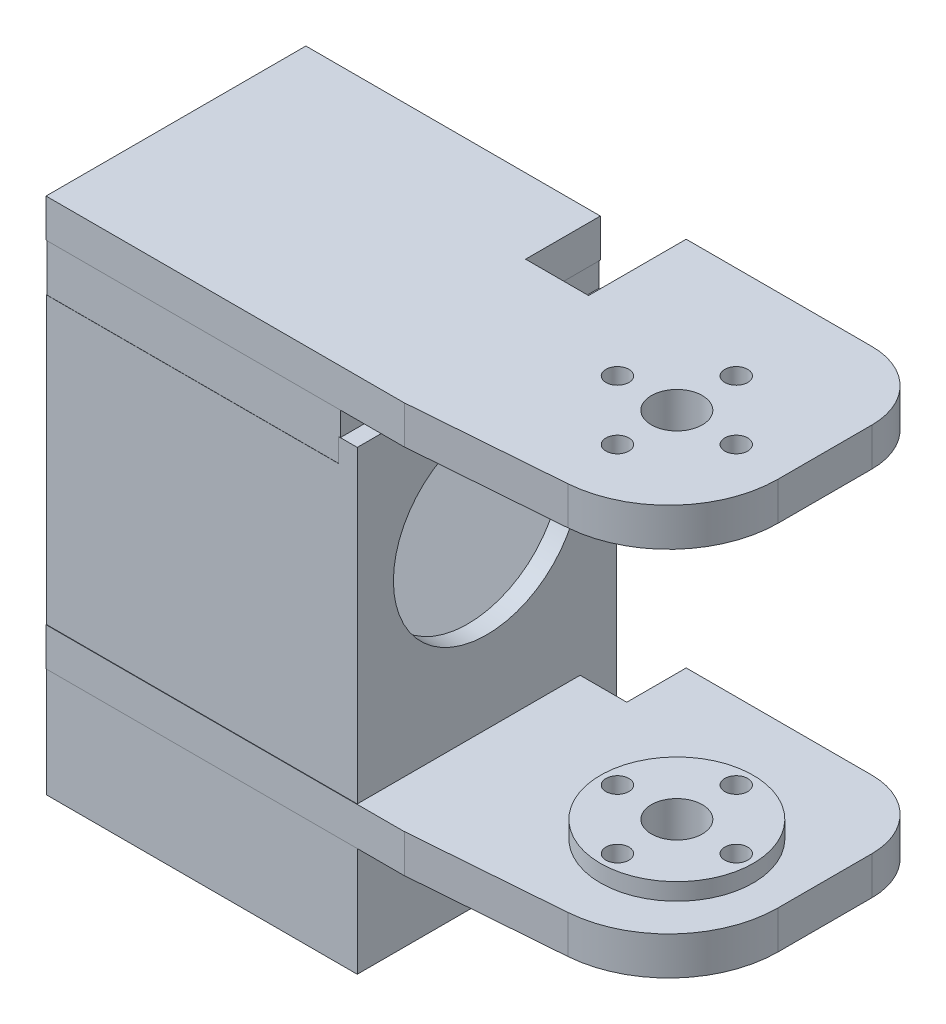
SolidWorks part; units mm, degrees
ref_plane "Front Plane" through (0, 0, 0) normal (0, 0, 1) x (1, 0, 0)
ref_plane "Top Plane" through (0, 0, 0) normal (0, 1, 0) x (1, 0, 0)
ref_plane "Right Plane" through (0, 0, 0) normal (1, 0, 0) x (0, 0, -1)
ref_plane "PY_p18_625" through (0, 18.625, 0) normal (0, 1, 0) x (1, 0, 0)
sketch "S_prism1" plane through (0, 18.625, 0) normal (0, 1, 0) x (1, 0, 0)
  line L0 (13, 10) -> (13, -1.0582)
  line L1 (1.0937, -13.9199) -> (-16.9, -15.31)
  line L2 (-16.9, -15.31) -> (-16.9, 18)
  line L3 (-16.9, 18) -> (5, 18)
  arc A0 (5, 18) -> (13, 10) centre (5.0002, 10.0002) cw
  arc A1 (13, -1.0582) -> (1.0937, -13.9199) centre (0.0999, -1.0582) cw
extrude "Boss_1" add sketch "S_prism1" along normal blind 4.5
ref_plane "PY_m20_625" through (0, -20.625, 0) normal (0, 1, 0) x (1, 0, 0)
sketch "S_cyl2" plane through (0, -20.625, 0) normal (0, 1, 0) x (1, 0, 0)
  circle A0 centre (0, 0) radius 9
  dimension "D1_S_cyl2" = 18
extrude "Boss_2" add sketch "S_cyl2" along normal blind 2
ref_plane "PY_m25_125" through (0, -25.125, 0) normal (0, 1, 0) x (1, 0, 0)
sketch "S_prism3" plane through (0, -25.125, 0) normal (0, 1, 0) x (1, 0, 0)
  line L0 (13, 10) -> (13, -1.0582)
  line L1 (1.0937, -13.9199) -> (-16.9, -15.31)
  line L2 (-16.9, -15.31) -> (-16.9, 18)
  line L3 (-16.9, 18) -> (5, 18)
  arc A0 (5, 18) -> (13, 10) centre (5.0002, 10.0002) cw
  arc A1 (13, -1.0582) -> (1.0937, -13.9199) centre (0.0999, -1.0582) cw
extrude "Boss_3" add sketch "S_prism3" along normal blind 4.5
sketch "S_prism4" plane through (0, 18.625, 0) normal (0, 1, 0) x (1, 0, 0)
  line L0 (-24.575, 6.5) -> (-16.8, 6.5)
  line L1 (-16.8, 6.5) -> (-16.8, -15.31)
  line L2 (-16.8, -15.31) -> (-24.575, -15.31)
  line L3 (-24.575, -15.31) -> (-24.575, 6.5)
extrude "Boss_4" add sketch "S_prism4" along normal blind 4.5
sketch "S_prism5" plane through (0, 18.625, 0) normal (0, 1, 0) x (1, 0, 0)
  line L0 (-59.025, -12.71) -> (-16.8, -12.71)
  line L1 (-16.8, -12.71) -> (-16.8, -15.31)
  line L2 (-16.8, -15.31) -> (-59.025, -15.31)
  line L3 (-59.025, -15.31) -> (-59.025, -12.71)
extrude "Boss_5" add sketch "S_prism5" along normal blind 4.5
sketch "S_prism6" plane through (0, 18.625, 0) normal (0, 1, 0) x (1, 0, 0)
  line L0 (-59.025, 15.31) -> (-24.325, 15.31)
  line L1 (-24.325, 15.31) -> (-24.325, -15.31)
  line L2 (-24.325, -15.31) -> (-59.025, -15.31)
  line L3 (-59.025, -15.31) -> (-59.025, 15.31)
extrude "Boss_6" add sketch "S_prism6" along normal blind 4.5
sketch "S_prism7" plane through (0, -25.125, 0) normal (0, 1, 0) x (1, 0, 0)
  line L0 (-24.575, 11) -> (-16.8, 11)
  line L1 (-16.8, 11) -> (-16.8, -15.31)
  line L2 (-16.8, -15.31) -> (-24.575, -15.31)
  line L3 (-24.575, -15.31) -> (-24.575, 11)
extrude "Boss_7" add sketch "S_prism7" along normal blind 4.5
sketch "S_prism8" plane through (0, -25.125, 0) normal (0, 1, 0) x (1, 0, 0)
  line L0 (-59.025, -12.71) -> (-16.8, -12.71)
  line L1 (-16.8, -12.71) -> (-16.8, -15.31)
  line L2 (-16.8, -15.31) -> (-59.025, -15.31)
  line L3 (-59.025, -15.31) -> (-59.025, -12.71)
extrude "Boss_8" add sketch "S_prism8" along normal blind 4.5
ref_plane "PZ_m15_260" through (0, 0, -15.26) normal (0, 0, 1) x (1, 0, 0)
sketch "S_box9" plane through (0, 0, -15.26) normal (0, 0, 1) x (1, 0, 0)
  line L0 (-59.025, 10.51) -> (-24.625, 10.51)
  line L1 (-24.625, 10.51) -> (-24.625, 13.01)
  line L2 (-24.625, 13.01) -> (-59.025, 13.01)
  line L3 (-59.025, 13.01) -> (-59.025, 10.51)
  dimension "P1" = 59.025
  dimension "P2" = 10.51
  dimension "P3" = 24.625
  dimension "P4" = 10.51
  dimension "P5" = 24.625
  dimension "P6" = 13.01
  dimension "P7" = 59.025
  dimension "P8" = 13.01
extrude "Boss_9" add sketch "S_box9" along normal blind 30.52
sketch "S_box10" plane through (0, 0, -15.26) normal (0, 0, 1) x (1, 0, 0)
  line L0 (-59.025, -38.01) -> (-24.625, -38.01)
  line L1 (-24.625, -38.01) -> (-24.625, 13.01)
  line L2 (-24.625, 13.01) -> (-59.025, 13.01)
  line L3 (-59.025, 13.01) -> (-59.025, -38.01)
  dimension "P1" = 59.025
  dimension "P2" = 38.01
  dimension "P3" = 24.625
  dimension "P4" = 38.01
  dimension "P5" = 24.625
  dimension "P6" = 13.01
  dimension "P7" = 59.025
  dimension "P8" = 13.01
extrude "Boss_10" add sketch "S_box10" along normal blind 2.5
ref_plane "PZ_p12_760" through (0, 0, 12.76) normal (0, 0, 1) x (1, 0, 0)
sketch "S_box11" plane through (0, 0, 12.76) normal (0, 0, 1) x (1, 0, 0)
  line L0 (-59.025, -38.01) -> (-24.625, -38.01)
  line L1 (-24.625, -38.01) -> (-24.625, 13.01)
  line L2 (-24.625, 13.01) -> (-59.025, 13.01)
  line L3 (-59.025, 13.01) -> (-59.025, -38.01)
  dimension "P1" = 59.025
  dimension "P2" = 38.01
  dimension "P3" = 24.625
  dimension "P4" = 38.01
  dimension "P5" = 24.625
  dimension "P6" = 13.01
  dimension "P7" = 59.025
  dimension "P8" = 13.01
extrude "Boss_11" add sketch "S_box11" along normal blind 2.5
sketch "S_box12" plane through (0, 0, -15.26) normal (0, 0, 1) x (1, 0, 0)
  line L0 (-59.025, -38.01) -> (-56.625, -38.01)
  line L1 (-56.625, -38.01) -> (-56.625, 13.01)
  line L2 (-56.625, 13.01) -> (-59.025, 13.01)
  line L3 (-59.025, 13.01) -> (-59.025, -38.01)
  dimension "P1" = 59.025
  dimension "P2" = 38.01
  dimension "P3" = 56.625
  dimension "P4" = 38.01
  dimension "P5" = 56.625
  dimension "P6" = 13.01
  dimension "P7" = 59.025
  dimension "P8" = 13.01
extrude "Boss_12" add sketch "S_box12" along normal blind 30.52
sketch "S_box13" plane through (0, 0, -15.26) normal (0, 0, 1) x (1, 0, 0)
  line L0 (-24.625, -38.01) -> (-22.4, -38.01)
  line L1 (-22.4, -38.01) -> (-22.4, 15.76)
  line L2 (-22.4, 15.76) -> (-24.625, 15.76)
  line L3 (-24.625, 15.76) -> (-24.625, -38.01)
  dimension "P1" = 24.625
  dimension "P2" = 38.01
  dimension "P3" = 22.4
  dimension "P4" = 38.01
  dimension "P5" = 22.4
  dimension "P6" = 15.76
  dimension "P7" = 24.625
  dimension "P8" = 15.76
extrude "Boss_13" add sketch "S_box13" along normal blind 30.52
ref_plane "PZ_m15_240" through (0, 0, -15.24) normal (0, 0, 1) x (1, 0, 0)
sketch "S_box14" plane through (0, 0, -15.24) normal (0, 0, 1) x (1, 0, 0)
  line L0 (-58.955, 12.9) -> (-24.395, 12.9)
  line L1 (-24.395, 12.9) -> (-24.395, 18.725)
  line L2 (-24.395, 18.725) -> (-58.955, 18.725)
  line L3 (-58.955, 18.725) -> (-58.955, 12.9)
  dimension "P1" = 58.955
  dimension "P2" = 12.9
  dimension "P3" = 24.395
  dimension "P4" = 12.9
  dimension "P5" = 24.395
  dimension "P6" = 18.725
  dimension "P7" = 58.955
  dimension "P8" = 18.725
extrude "Boss_14" add sketch "S_box14" along normal blind 30.48
ref_plane "PY_p18_525" through (0, 18.525, 0) normal (0, 1, 0) x (1, 0, 0)
sketch "S_hole15" plane through (0, 18.525, 0) normal (0, 1, 0) x (1, 0, 0)
  circle A0 centre (0, 0) radius 3
  dimension "D1_S_hole15" = 6
extrude "Hole_15" cut sketch "S_hole15" along normal blind 4.7
sketch "S_hole16" plane through (0, 18.525, 0) normal (0, 1, 0) x (1, 0, 0)
  circle A0 centre (7, 0) radius 1.35
  dimension "D1_S_hole16" = 2.7
  dimension "P2" = 7
extrude "Hole_16" cut sketch "S_hole16" along normal blind 4.7
sketch "S_hole17" plane through (0, 18.525, 0) normal (0, 1, 0) x (1, 0, 0)
  circle A0 centre (0, -7) radius 1.35
  dimension "D1_S_hole17" = 2.7
  dimension "P2" = 7
extrude "Hole_17" cut sketch "S_hole17" along normal blind 4.7
sketch "S_hole18" plane through (0, 18.525, 0) normal (0, 1, 0) x (1, 0, 0)
  circle A0 centre (-7, 0) radius 1.35
  dimension "D1_S_hole18" = 2.7
  dimension "P2" = 7
extrude "Hole_18" cut sketch "S_hole18" along normal blind 4.7
sketch "S_hole19" plane through (0, 18.525, 0) normal (0, 1, 0) x (1, 0, 0)
  circle A0 centre (0, 7) radius 1.35
  dimension "D1_S_hole19" = 2.7
  dimension "P2" = 7
extrude "Hole_19" cut sketch "S_hole19" along normal blind 4.7
ref_plane "PY_m25_225" through (0, -25.225, 0) normal (0, 1, 0) x (1, 0, 0)
sketch "S_hole20" plane through (0, -25.225, 0) normal (0, 1, 0) x (1, 0, 0)
  circle A0 centre (0, 0) radius 3
  dimension "D1_S_hole20" = 6
extrude "Hole_20" cut sketch "S_hole20" along normal blind 6.7
sketch "S_hole21" plane through (0, -25.225, 0) normal (0, 1, 0) x (1, 0, 0)
  circle A0 centre (7, 0) radius 1.35
  dimension "D1_S_hole21" = 2.7
  dimension "P2" = 7
extrude "Hole_21" cut sketch "S_hole21" along normal blind 6.7
sketch "S_hole22" plane through (0, -25.225, 0) normal (0, 1, 0) x (1, 0, 0)
  circle A0 centre (0, -7) radius 1.35
  dimension "D1_S_hole22" = 2.7
  dimension "P2" = 7
extrude "Hole_22" cut sketch "S_hole22" along normal blind 6.7
sketch "S_hole23" plane through (0, -25.225, 0) normal (0, 1, 0) x (1, 0, 0)
  circle A0 centre (-7, 0) radius 1.35
  dimension "D1_S_hole23" = 2.7
  dimension "P2" = 7
extrude "Hole_23" cut sketch "S_hole23" along normal blind 6.7
sketch "S_hole24" plane through (0, -25.225, 0) normal (0, 1, 0) x (1, 0, 0)
  circle A0 centre (0, 7) radius 1.35
  dimension "D1_S_hole24" = 2.7
  dimension "P2" = 7
extrude "Hole_24" cut sketch "S_hole24" along normal blind 6.7
ref_plane "PX_m59_125" through (-59.125, 0, 0) normal (1, 0, 0) x (0, 0, -1)
sketch "S_hole25" plane through (-59.125, 0, 0) normal (1, 0, 0) x (0, 0, -1)
  circle A0 centre (0, 0) radius 11
  dimension "D1_S_hole25" = 22
extrude "Hole_25" cut sketch "S_hole25" along normal blind 2.6
sketch "S_hole26" plane through (-59.125, 0, 0) normal (1, 0, 0) x (0, 0, -1)
  circle A0 centre (-10.25, -8.3) radius 1.1
  dimension "D1_S_hole26" = 2.2
  dimension "P2" = 10.25
  dimension "P3" = 8.3
extrude "Hole_26" cut sketch "S_hole26" along normal blind 2.6
sketch "S_hole27" plane through (-59.125, 0, 0) normal (1, 0, 0) x (0, 0, -1)
  circle A0 centre (10.25, -32.75) radius 1.1
  dimension "D1_S_hole27" = 2.2
  dimension "P2" = 10.25
  dimension "P3" = 32.75
extrude "Hole_27" cut sketch "S_hole27" along normal blind 2.6
sketch "S_hole28" plane through (-59.125, 0, 0) normal (1, 0, 0) x (0, 0, -1)
  circle A0 centre (-10.25, -32.75) radius 1.1
  dimension "D1_S_hole28" = 2.2
  dimension "P2" = 10.25
  dimension "P3" = 32.75
extrude "Hole_28" cut sketch "S_hole28" along normal blind 2.6
ref_plane "PX_m24_725" through (-24.725, 0, 0) normal (1, 0, 0) x (0, 0, -1)
sketch "S_hole29" plane through (-24.725, 0, 0) normal (1, 0, 0) x (0, 0, -1)
  circle A0 centre (0, 0) radius 11
  dimension "D1_S_hole29" = 22
extrude "Hole_29" cut sketch "S_hole29" along normal blind 2.425
sketch "S_pcut30" plane through (-59.125, 0, 0) normal (1, 0, 0) x (0, 0, -1)
  line L0 (15.86, -38.61) -> (15.86, -28.41)
  line L1 (15.86, -28.41) -> (5.66, -38.61)
  line L2 (5.66, -38.61) -> (15.86, -38.61)
extrude "Cut_30" cut sketch "S_pcut30" along normal blind 34.6
equation "\"plate_t\" = 3"
equation "\"clearance\" = 0.4"
